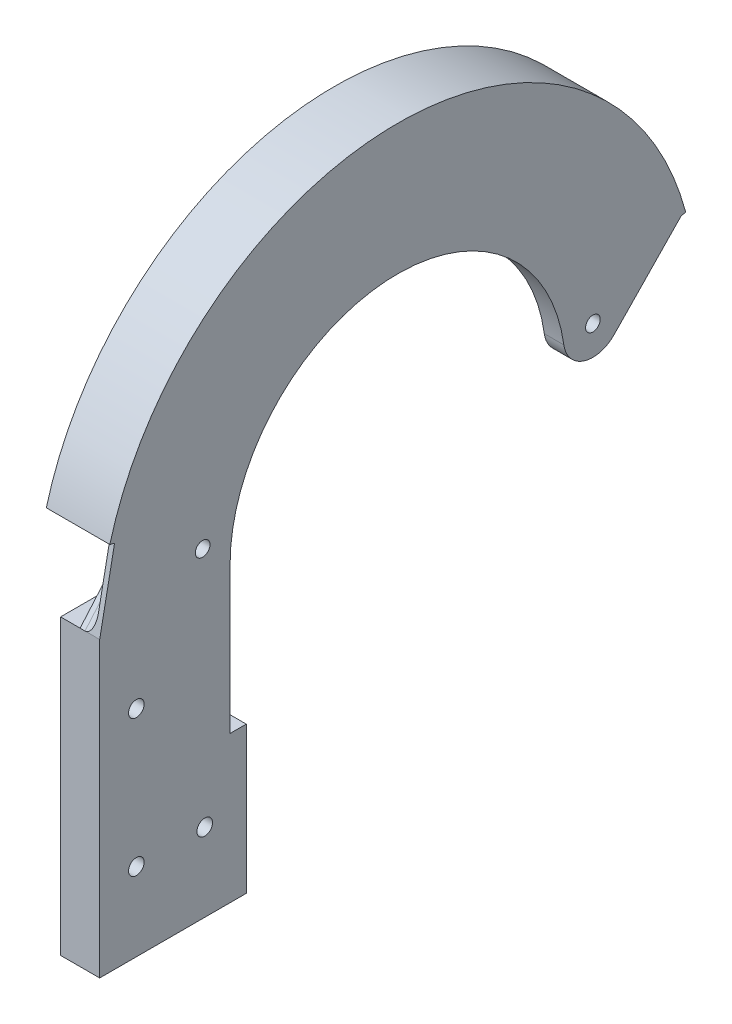
SolidWorks part; units mm, degrees
ref_plane "Front" through (0, 0, 0) normal (0, 0, 1) x (1, 0, 0)
ref_plane "Top" through (0, 0, 0) normal (0, 1, 0) x (1, 0, 0)
ref_plane "Right" through (0, 0, 0) normal (1, 0, 0) x (0, 0, -1)
sketch "Sketch1" plane through (0, 0, 0) normal (1, 0, 0) x (0, 0, -1)
  line L0 (-33.9877, 64.7011) -> (-45.8745, 66.3452) construction
  line L2 (-61, 0) -> (-31, 0)
  line L3 (-61, 60) -> (-61, 0)
  line L4 (-24.1481, 66.4705) -> (-53.1259, 74.235) construction
  line L5 (-38.637, 70.3528) -> (-39.9311, 65.5231) construction
  line L8 (-31, 30) -> (-31, 0)
  line L9 (0, 50) -> (0, -50) construction
  line L12 (-61, 0) -> (-31, 0) construction
  line L13 (-61, 0) -> (-61, 60) construction
  line L15 (0, 60) -> (-53.1259, 74.235) construction
  line L16 (65, 60) -> (-65, 60) construction
  line L17 (-31, 30) -> (-46, 30) construction
  line L18 (-34.3113, 60) -> (-34.3113, 30)
  line L19 (-34.3113, 30) -> (-31, 30)
  line L20 (-61, 60) -> (-35.1596, 90.142)
  arc A0 (24.1481, 66.4705) -> (-24.1481, 66.4705) centre (0, 60) ccw construction
  arc A1 (53.1259, 74.235) -> (-53.1259, 74.235) centre (0, 60) ccw construction
  arc A2 (24.8594, 62.6474) -> (-24.1481, 66.4705) centre (0, 60) ccw construction
  arc A3 (53.1259, 74.235) -> (-53.1259, 74.235) centre (0, 60) ccw
  circle A6 centre (-39.9311, 65.5231) radius 1.5
  arc A7 (-46.3113, 60) -> (45.8745, 66.3452) centre (0, 60) cw
  circle A8 centre (39.9311, 65.5231) radius 1.5
  arc A9 (33.9877, 64.7011) -> (45.8745, 66.3452) centre (39.9311, 65.5231) ccw
  arc A10 (-34.3113, 60) -> (33.9877, 64.7011) centre (0, 60) cw
  dimension "D3" = 3
  dimension "D1" = 12
  dimension "D4" = 5
  dimension "D7" = 30
extrude "Boss-Extrude1" add sketch "Sketch1" along normal blind 4 from offset 35 contours A9 L3 L2 L8 A6 A8 region at (0, 30, 59.4921) offset against normal yes
sketch "Sketch2" plane through (-31, 0, 0) normal (1, 0, 0) x (0, 0, -1)
  line L0 (-61, 60) -> (-35.1596, 90.142) construction
  line L1 (-61, 60) -> (-35.1596, 90.142)
  line L2 (-57.9555, 75.5291) -> (-58.9215, 75.788)
  line L3 (58.9215, 75.788) -> (57.9555, 75.5291)
  line L4 (-57.9555, 75.5291) -> (-61, 60)
  line L5 (57.9555, 75.5291) -> (44.244, 61.3519)
  arc A0 (45.8745, 66.3452) -> (-35.1596, 90.142) centre (0, 60) ccw construction
  arc A1 (45.8745, 66.3452) -> (-35.1596, 90.142) centre (0, 60) ccw
  arc A2 (33.9877, 64.7011) -> (45.8745, 66.3452) centre (39.9311, 65.5231) ccw construction
  arc A4 (57.9555, 75.5291) -> (-57.9555, 75.5291) centre (0, 60) ccw
  arc A5 (57.9555, 75.5291) -> (-57.9555, 75.5291) centre (0, 60) ccw
  arc A6 (58.9215, 75.788) -> (-58.9215, 75.788) centre (0, 60) ccw
  arc A7 (58.9215, 75.788) -> (-58.9215, 75.788) centre (0, 60) ccw
  arc M9 (45.8745, 66.3452) -> (-35.1596, 90.142) centre (0, 60) ccw
  line M10 (-35.1596, 90.142) -> (-61, 60)
  arc M17 (33.9877, 64.7011) -> (45.8745, 66.3452) centre (39.9311, 65.5231) ccw
  dimension "D1" = 5
  dimension "D2" = 6
extrude "Boss-Extrude2" add sketch "Sketch2" against normal blind 1 contours L3 A7 L2 L4 L5 M10 M9 M17 region at (-31, 67.5083, 58.1704)
extrude "Boss-Extrude3" add sketch "Sketch2<3>" against normal blind 13 contours L3 A7 L2 A5 region at (-31, 76.8786, 58.1116)
sketch "Sketch2<3>" plane through (-31, 0, 0) normal (1, 0, 0) x (0, 0, -1) same geometry as "Sketch2"
fillet "Fillet1" radius 1 1 edges at (-32, 120, 0)
fillet "Fillet2" radius 2 3 edges at (-32, 63.6606, -45.6347) (-32, 75.071, 48.0798) (-32, 104.4349, -13.0489)
sketch "Sketch3" plane through (-35, 0, 0) normal (-1, 0, 0) x (0, 0, 1)
  line L0 (46, 60) -> (46, 30) construction
  line L1 (46, 30) -> (31, 30) construction
  line L2 (61, 60) -> (46, 60) construction
  line L3 (46, 60) -> (46, 30)
  line L4 (46, 30) -> (31, 30)
  line L5 (61, 60) -> (46, 60)
  line L6 (31, 30) -> (31, 0) construction
  line L7 (61, 0) -> (31, 0) construction
  line L8 (61, 60) -> (61, 0) construction
  line L9 (31, 30) -> (31, 0)
  line L10 (61, 0) -> (31, 0)
  line L11 (61, 60) -> (61, 0)
extrude "Boss-Extrude4" add sketch "Sketch3" along normal up to surface (4 mm away)
sketch "Sketch5" plane through (-31, 0, 0) normal (1, 0, 0) x (0, 0, -1)
  circle A0 centre (-53.5, 44) radius 1.6 construction
  circle A1 centre (-53.5, 16) radius 1.6 construction
  circle A2 centre (-39.5, 16) radius 1.6 construction
  circle A3 centre (-53.5, 44) radius 1.6
  circle A4 centre (-53.5, 16) radius 1.6
  circle A5 centre (-39.5, 16) radius 1.6
extrude "Cut-Extrude1" cut sketch "Sketch5" against normal through all
equation "\"D1@Sketch2\"=\"D2@Sketch2\"-1"
